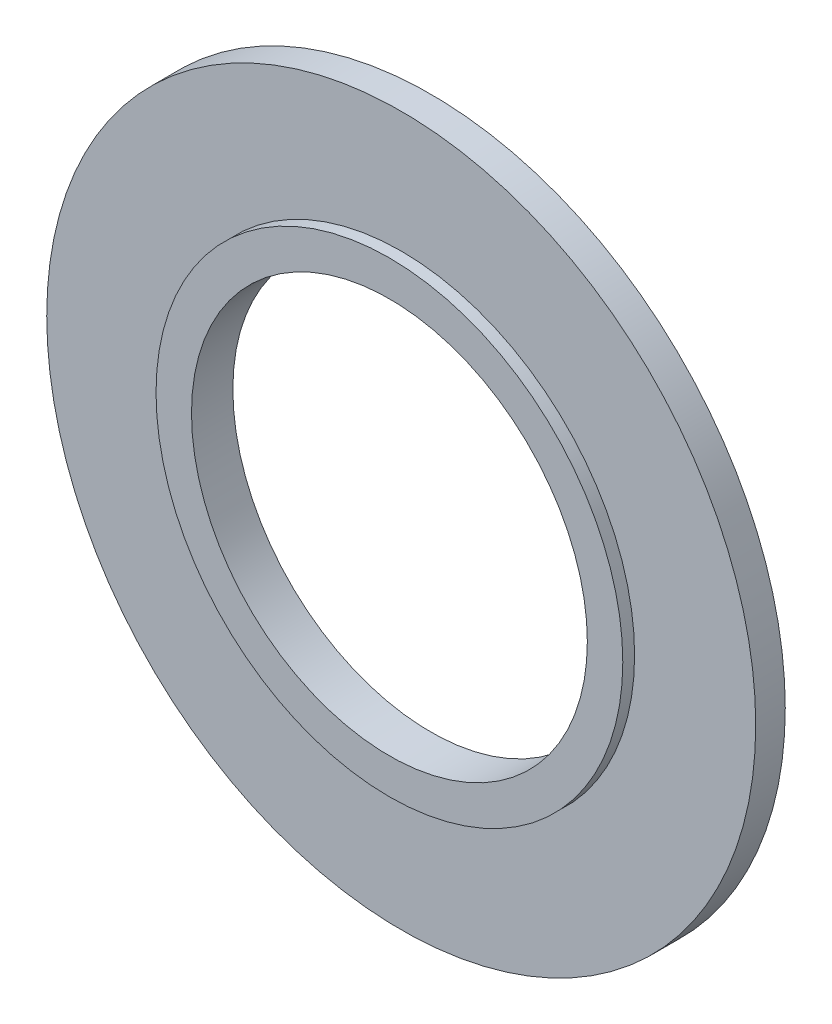
SolidWorks part; units mm, degrees
material "6061-T6 (SS)"
ref_plane "Front Plane" through (0, 0, 0) normal (0, 0, 1) x (1, 0, 0)
ref_plane "Top Plane" through (0, 0, 0) normal (0, 1, 0) x (1, 0, 0)
ref_plane "Right Plane" through (0, 0, 0) normal (1, 0, 0) x (0, 0, -1)
sketch "Sketch1" plane through (0, 0, 0) normal (0, 0, 1) x (1, 0, 0)
  circle A0 centre (0, 0) radius 16.75
  circle A1 centre (0, 0) radius 30
  dimension "D1" = 33.5
  dimension "D2" = 60
extrude "Boss-Extrude1" add sketch "Sketch1" along normal blind 3.5
sketch "Sketch2" plane through (0, 0, 3.5) normal (0, 0, 1) x (1, 0, 0)
  circle A0 centre (0, 0) radius 19.75
  circle A2 centre (0, 0) radius 30
  circle A3 centre (0, 0) radius 30
  dimension "D1" = 39.5
  dimension "D2" = 0
extrude "Cut-Extrude1" cut sketch "Sketch2" against normal blind 1
